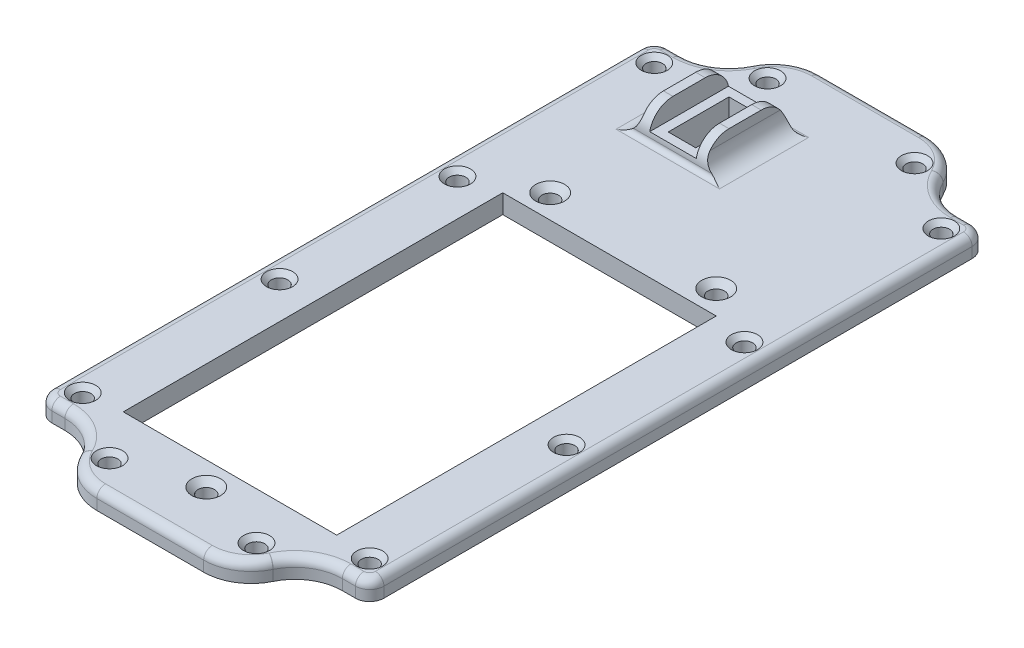
SolidWorks part; units mm, degrees
ref_plane "Спереди" through (0, 0, 0) normal (0, 0, 1) x (1, 0, 0)
ref_plane "Сверху" through (0, 0, 0) normal (0, 1, 0) x (1, 0, 0)
ref_plane "Справа" through (0, 0, 0) normal (1, 0, 0) x (0, 0, -1)
sketch "Эскиз1" plane through (0, 0, 0) normal (0, 1, 0) x (1, 0, 0)
  line L0 (-29.2421, -65) -> (-32, -65)
  line L1 (-11.2579, -76.2495) -> (11.2579, -76.2495)
  line L2 (32, -65) -> (29.2421, -65)
  line L3 (35, -62) -> (35, 62)
  line L4 (32, 65) -> (29.2421, 65)
  line L5 (-35, -62) -> (-35, 62)
  line L6 (-29.2421, 65) -> (-32, 65)
  line L7 (-11.2579, 76.2495) -> (11.2579, 76.2495)
  line L8 (-20.2583, -70.6078) -> (-20.2417, -70.6418)
  line L9 (20.2583, -70.6078) -> (20.2417, -70.6418)
  line L10 (20.2417, 70.6418) -> (20.2583, 70.6078)
  line L11 (-20.2583, 70.6078) -> (-20.2417, 70.6418)
  arc A0 (-35, -62) -> (-32, -65) centre (-32, -62) ccw
  circle A1 centre (-30.25, -60.25) radius 1.75
  arc A2 (-20.2583, -70.6078) -> (-29.2421, -65) centre (-29.2421, -75) ccw
  circle A3 centre (-15.4902, -69.356) radius 1.75
  arc A4 (-20.2417, -70.6418) -> (-11.2579, -76.2495) centre (-11.2579, -66.2495) ccw
  circle A5 centre (15.4902, -69.356) radius 1.75
  arc A6 (11.2579, -76.2495) -> (20.2417, -70.6418) centre (11.2579, -66.2495) ccw
  arc A7 (29.2421, -65) -> (20.2583, -70.6078) centre (29.2421, -75) ccw
  arc A8 (32, -65) -> (35, -62) centre (32, -62) ccw
  circle A9 centre (30.25, -60.25) radius 1.75
  circle A10 centre (30.25, -18.75) radius 1.75
  circle A11 centre (-30.25, -18.75) radius 1.75
  circle A12 centre (30.25, 18.75) radius 1.75
  circle A13 centre (-30.25, 18.75) radius 1.75
  arc A14 (35, 62) -> (32, 65) centre (32, 62) ccw
  circle A15 centre (30.25, 60.25) radius 1.75
  arc A16 (20.2583, 70.6078) -> (29.2421, 65) centre (29.2421, 75) ccw
  arc A17 (20.2417, 70.6418) -> (11.2579, 76.2495) centre (11.2579, 66.2495) ccw
  circle A18 centre (15.4902, 69.356) radius 1.75
  arc A19 (-32, 65) -> (-35, 62) centre (-32, 62) ccw
  circle A20 centre (-30.25, 60.25) radius 1.75
  arc A21 (-29.2421, 65) -> (-20.2583, 70.6078) centre (-29.2421, 75) ccw
  circle A22 centre (-15.4902, 69.356) radius 1.75
  arc A23 (-11.2579, 76.2495) -> (-20.2417, 70.6418) centre (-11.2579, 66.2495) ccw
extrude "Бобышка-Вытянуть1" add sketch "Эскиз1" along normal blind 4
fillet "Скругление1" radius 1.8 24 edges at (34.1213, 4, 64.1213) (30.621, 4, 65) (23.9469, 4, 66.517) (20.25, 4, 70.6248) (16.5531, 4, 74.7325) (0, 4, 76.2495) (-16.5531, 4, 74.7325) (-20.25, 4, 70.6248) (-23.9469, 4, 66.517) (-30.621, 4, 65) (-34.1213, 4, 64.1213) (-35, 4, 0) (-34.1213, 4, -64.1213) (-30.621, 4, -65) (-23.9469, 4, -66.517) (-20.25, 4, -70.6248) (-16.5531, 4, -74.7325) (0, 4, -76.2495) (16.5531, 4, -74.7325) (20.25, 4, -70.6248) (23.9469, 4, -66.517) (30.621, 4, -65) (34.1213, 4, -64.1213) (35, 4, 0)
sketch "Эскиз3" plane through (0, 4, 0) normal (0, 1, 0) x (1, 0, 0)
  line L0 (0, 74.4495) -> (0, -74.4495) construction
  line L1 (11.2579, 74.4495) -> (-11.2579, 74.4495) construction
  line L2 (-11.2579, -74.4495) -> (11.2579, -74.4495) construction
  line L4 (-22.5, -59.4495) -> (22.5, -59.4495)
  line L5 (-22.5, -59.4495) -> (-22.5, 20.5505)
  line L6 (-22.5, 20.5505) -> (22.5, 20.5505)
  line L7 (22.5, -59.4495) -> (22.5, 20.5505)
  line L8 (-22.5, -59.4495) -> (22.5, 20.5505) construction
  line L9 (-22.5, 20.5505) -> (22.5, -59.4495) construction
  point P6 (0, -19.4495)
  point P11 (0, -59.4495)
  dimension "D1" = 80
  dimension "D2" = 45
  dimension "D3" = 15
extrude "Вырез-Вытянуть2" cut sketch "Эскиз3" against normal through all
sketch "Эскиз4" plane through (0, 4, 0) normal (0, 1, 0) x (1, 0, 0)
  line L0 (-11.2579, 74.4495) -> (-11.2579, 20.5505) construction
  line L2 (-14.1579, 59.8913) -> (-8.3579, 59.8913)
  line L3 (22.5, 20.5505) -> (-22.5, 20.5505) construction
  line L4 (-14.1579, 59.8913) -> (-14.1579, 47.0913)
  line L5 (-14.1579, 47.0913) -> (-8.3579, 47.0913)
  line L6 (-8.3579, 59.8913) -> (-8.3579, 47.0913)
  line L7 (-14.1579, 59.8913) -> (-8.3579, 47.0913) construction
  line L8 (-14.1579, 47.0913) -> (-8.3579, 59.8913) construction
  point P4 (-11.2579, 53.4913)
  dimension "D1" = 5.8
  dimension "D2" = 12.8
extrude "Вырез-Вытянуть3" cut sketch "Эскиз4" against normal blind 3
chamfer "Фаска1" distance 1 angle 45 12 edges at (-30.25, 4, 62) (-15.4902, 4, 71.106) (15.4902, 4, 71.106) (30.25, 4, 62) (30.25, 4, 20.5) (-30.25, 4, 20.5) (-30.25, 4, -17) (30.25, 4, -17) (30.25, 4, -58.5) (15.4902, 4, -67.606) (-30.25, 4, -58.5) (-15.4902, 4, -67.606)
sketch "Эскиз5" plane through (0, 1, 0) normal (0, 1, 0) x (1, 0, 0)
  line L0 (-11.2579, 59.8913) -> (-11.2579, 47.0913) construction
  line L1 (-8.3579, 59.8913) -> (-14.1579, 59.8913) construction
  line L2 (-14.1579, 47.0913) -> (-8.3579, 47.0913) construction
  line L3 (-14.1579, 59.8913) -> (-14.1579, 47.0913) construction
  line L4 (-8.3579, 49.4913) -> (-14.1579, 49.4913)
  line L5 (-8.3579, 49.4913) -> (-8.3579, 57.4913)
  line L6 (-8.3579, 57.4913) -> (-14.1579, 57.4913)
  line L7 (-14.1579, 49.4913) -> (-14.1579, 57.4913)
  line L8 (-8.3579, 49.4913) -> (-14.1579, 57.4913) construction
  line L9 (-8.3579, 57.4913) -> (-14.1579, 49.4913) construction
  point P6 (-11.2579, 53.4913)
  dimension "D1" = 8
extrude "Вырез-Вытянуть4" cut sketch "Эскиз5" against normal through all
sketch "Эскиз6" plane through (0, 4, 0) normal (0, 1, 0) x (1, 0, 0)
  line L1 (-8.3579, 47.0913) -> (-14.1579, 47.0913)
  line L2 (-8.3579, 47.0913) -> (-8.3579, 59.8913)
  line L3 (-8.3579, 59.8913) -> (-14.1579, 59.8913)
  line L4 (-14.1579, 47.0913) -> (-14.1579, 59.8913)
  line L5 (-8.3579, 47.0913) -> (-14.1579, 59.8913) construction
  line L6 (-8.3579, 59.8913) -> (-14.1579, 47.0913) construction
  line L7 (-6.3579, 45.0913) -> (-16.1579, 45.0913)
  line L8 (-6.3579, 45.0913) -> (-6.3579, 61.8913)
  line L9 (-6.3579, 61.8913) -> (-16.1579, 61.8913)
  line L10 (-16.1579, 45.0913) -> (-16.1579, 61.8913)
  line L11 (-6.3579, 45.0913) -> (-16.1579, 61.8913) construction
  line L12 (-6.3579, 61.8913) -> (-16.1579, 45.0913) construction
  point P0 (-11.2579, 53.4913)
  point P6 (-11.2579, 53.4913)
  point P11 (-6.3579, 53.4913)
  dimension "D1" = 2
  dimension "D2" = 12.8
  dimension "D3" = 5.8
  dimension "D4" = 2
extrude "Бобышка-Вытянуть2" add sketch "Эскиз6" along normal blind 2
sketch "Эскиз8" plane through (0, 4, 0) normal (0, 1, 0) x (1, 0, 0)
  line L1 (-16.1579, 45.0913) -> (-18.1579, 45.0913)
  line L2 (-16.1579, 45.0913) -> (-16.1579, 61.8913)
  line L3 (-16.1579, 61.8913) -> (-18.1579, 61.8913)
  line L4 (-18.1579, 45.0913) -> (-18.1579, 61.8913)
  line L5 (-6.3579, 61.8913) -> (-4.3579, 61.8913)
  line L6 (-6.3579, 61.8913) -> (-6.3579, 45.0913)
  line L7 (-6.3579, 45.0913) -> (-4.3579, 45.0913)
  line L8 (-4.3579, 61.8913) -> (-4.3579, 45.0913)
  dimension "D1" = 2
  dimension "D2" = 2
extrude "Бобышка-Вытянуть3" add sketch "Эскиз8" along normal blind 6
fillet "Скругление3" radius 5 2 edges at (-17.1579, 10, -61.8913) (-17.1579, 10, -45.0913)
fillet "Скругление4" radius 1 2 edges at (-11.2579, 4, -61.8913) (-11.2579, 4, -45.0913)
fillet "Скругление5" radius 4 2 edges at (-4.3579, 4, -53.4913) (-18.1579, 4, -53.4913)
sketch "Эскиз9" plane through (0, 4, 0) normal (0, 1, 0) x (1, 0, 0)
  line L0 (22.5, 20.5505) -> (-22.5, 20.5505) construction
  line L1 (-22.5, -59.4495) -> (22.5, -59.4495) construction
  circle A0 centre (-17.5, 25.5505) radius 1.75
  circle A1 centre (17.5, 25.5505) radius 1.75
  circle A2 centre (0, -64.4495) radius 1.75
  point P12 (0, -59.4495)
  dimension "D3" = 3.5
  dimension "D4" = 3.5
  dimension "D7" = 3.5
  dimension "D1" = 5
  dimension "D2" = 5
  dimension "D5" = 5
  dimension "D6" = 5
  dimension "D8" = 5
extrude "Вырез-Вытянуть5" cut sketch "Эскиз9" against normal through all
chamfer "Фаска2" distance 1.3 angle 45 3 edges at (0, 4, 66.1995) (17.5, 4, -23.8005) (-17.5, 4, -23.8005)
